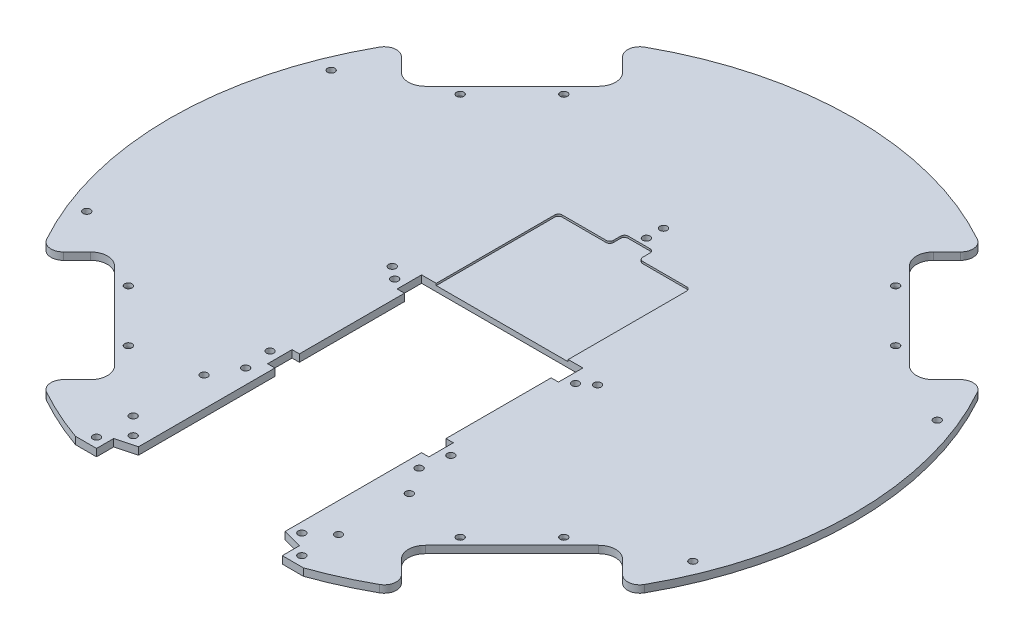
SolidWorks part; units mm, degrees
material "1060 Alloy"
ref_plane "Front Plane" through (0, 0, 0) normal (0, 0, 1) x (1, 0, 0)
ref_plane "Top Plane" through (0, 0, 0) normal (0, 1, 0) x (1, 0, 0)
ref_plane "Right Plane" through (0, 0, 0) normal (1, 0, 0) x (0, 0, -1)
sketch "Sketch1" plane through (0, 0, 0) normal (0, 1, 0) x (1, 0, 0)
  circle A0 centre (0, 0) radius 140
  dimension "D1" = 280
extrude "Boss-Extrude1" add sketch "Sketch1" along normal blind 3
sketch "Sketch7" plane through (0, 3, 0) normal (0, 1, 0) x (1, 0, 0)
  line L0 (-99.0303, -63.6043) -> (-63.6043, -99.0303)
  line L1 (-108.8591, -63.6043) -> (-121.6224, -76.3675)
  line L2 (-63.6043, -108.8591) -> (-76.3675, -121.6224)
  line L3 (-121.6224, -76.3675) -> (-76.3675, -121.6224)
  line L4 (0, 0) -> (-98.9949, -98.9949) construction
  line L7 (0, 0) -> (0, 130) construction
  circle A0 centre (0, 0) radius 140 construction
  arc A1 (-108.8591, -63.6043) -> (-99.0303, -63.6043) centre (-103.9447, -68.5186) cw
  arc A2 (-63.6043, -99.0303) -> (-63.6043, -108.8591) centre (-68.5186, -103.9447) cw
  dimension "D4" = 6.95
  dimension "D1" = 115
  dimension "D2" = 64
  dimension "D3" = 135
extrude "Cut-Extrude4" cut sketch "Sketch7" against normal up to next
sketch "Sketch9" plane through (0, 3, 0) normal (0, 1, 0) x (1, 0, 0)
  line L1 (-63.6043, -99.0303) -> (-99.0303, -63.6043) construction
  line L4 (-108.8591, -63.6043) -> (-119.0017, -73.7469) construction
  circle A0 centre (-89.0955, -67.8823) radius 1.5
  circle A1 centre (-67.8823, -89.0955) radius 1.5
  dimension "D4" = 3
  dimension "D1" = 4
  dimension "D2" = 30
  dimension "D3" = 17
  dimension "D5" = 4
extrude "Cut-Extrude6" cut sketch "Sketch9" against normal up to next
fillet "Fillet1" radius 5 2 edges at (-73.7469, 1.5, 119.0017) (-119.0017, 1.5, 73.7469)
pattern_circular "CirPattern1" count 4 over 360 about axis through (0, 3, 0) along (0, 1, 0) of "Cut-Extrude4", "Fillet1", "Cut-Extrude6"
sketch "Sketch2" plane through (0, 3, 0) normal (0, 1, 0) x (1, 0, 0)
  line L0 (-46.6476, -132) -> (-38, -132)
  line L1 (-30, -122.8564) -> (-30, -67)
  line L2 (-33, -4) -> (33, -4)
  line L3 (30, -67) -> (30, -122.8564)
  line L4 (38, -132) -> (46.6476, -132)
  line L5 (46.6476, -132) -> (46.6476, -140)
  line L6 (46.6476, -140) -> (-46.6476, -140)
  line L7 (-46.6476, -140) -> (-46.6476, -132)
  line L8 (-33, -57) -> (-33, -67)
  line L9 (-33, -67) -> (-30, -67)
  line L10 (33, -57) -> (33, -67)
  line L11 (33, -67) -> (30, -67)
  line L12 (-33, -57) -> (-30, -57)
  line L13 (-30, -57) -> (-30, -14)
  line L14 (-30, -14) -> (-33, -14)
  line L15 (-33, -14) -> (-33, -4)
  line L16 (33, -4) -> (33, -14)
  line L17 (33, -14) -> (30, -14)
  line L18 (30, -14) -> (30, -57)
  line L19 (30, -57) -> (33, -57)
  line L20 (-38, -132) -> (-38, -125)
  line L21 (-38, -125) -> (-30, -122.8564)
  line L22 (38, -132) -> (38, -125)
  line L23 (38, -125) -> (30, -122.8564)
  circle A0 centre (0, 0) radius 140 construction
  dimension "D8" = 3
  dimension "D5" = 63
  dimension "D6" = 66
  dimension "D1" = 8
  dimension "D2" = 65
  dimension "D3" = 60
  dimension "D4" = 16.6476
  dimension "D7" = 10
  dimension "D9" = 76
  dimension "D10" = 7
  dimension "D11" = 105
extrude "Cut-Extrude1" cut sketch "Sketch2" against normal up to next
fillet "Fillet3" radius 1.5 8 edges at (67.8823, 0, 90.5955) (89.0955, 0, 69.3823) (89.0955, 0, -66.3823) (67.8823, 0, -87.5955) (-67.8823, 0, -87.5955) (-89.0955, 0, -66.3823) (-67.8823, 0, 90.5955) (-89.0955, 0, 69.3823)
sketch "Sketch10" plane through (0, 3, 0) normal (0, 1, 0) x (1, 0, 0)
  line L0 (-33, -57) -> (-33, -67) construction
  line L1 (33, -67) -> (33, -57) construction
  line L2 (-33, -67) -> (-30, -67) construction
  line L4 (-30, -14) -> (-33, -14) construction
  line L5 (33, -4) -> (-33, -4) construction
  circle A0 centre (-37, -62) radius 1.5
  circle A1 centre (37, -62) radius 1.5
  circle A2 centre (-37, -11) radius 1.5
  circle A3 centre (37, -11) radius 1.5
  circle A4 centre (-42, -7) radius 1.5
  circle A5 centre (42, -7) radius 1.5
  point P17 (-31.5, -14)
  dimension "D3" = 3
  dimension "D1" = 4
  dimension "D2" = 4
  dimension "D4" = 5
  dimension "D5" = 3
  dimension "D6" = 3
  dimension "D7" = 5
  dimension "D8" = 5
extrude "Cut-Extrude7" cut sketch "Sketch10" against normal up to next
sketch "Sketch13" plane through (0, 3, 0) normal (0, 1, 0) x (1, 0, 0)
  line L0 (-38, -132) -> (-46.6476, -132) construction
  line L1 (-38, -132) -> (-46.6476, -132) construction
  circle A0 centre (-42, -84) radius 1.5
  circle A1 centre (-42, -113) radius 1.5
  circle A2 centre (42, -113) radius 1.5
  circle A3 centre (42, -84) radius 1.5
  dimension "D1" = 3
  dimension "D2" = 19
  dimension "D3" = 48
  dimension "D4" = 42
  dimension "D5" = 42
extrude "Cut-Extrude9" cut sketch "Sketch13" against normal up to next
sketch "Sketch16" plane through (0, 3, 0) normal (0, 1, 0) x (1, 0, 0)
  circle A0 centre (0, 62) radius 1.5
  circle A4 centre (0, 55) radius 1.5
  dimension "D2" = 3
  dimension "D5" = 3
  dimension "D1" = 62
  dimension "D7" = 55
extrude "Cut-Extrude12" cut sketch "Sketch16" against normal up to next
sketch "Sketch17" plane through (0, 3, 0) normal (0, 1, 0) x (1, 0, 0)
  circle A0 centre (-124, 50) radius 1.5
  circle A1 centre (-124, -50) radius 1.5
  circle A2 centre (124, 50) radius 1.5
  circle A3 centre (124, -50) radius 1.5
  dimension "D1" = 3
  dimension "D2" = 50
  dimension "D3" = 50
  dimension "D4" = 124
  dimension "D5" = 124
extrude "Cut-Extrude13" cut sketch "Sketch17" against normal up to next
sketch "Sketch18" plane through (0, 3, 0) normal (0, 1, 0) x (1, 0, 0)
  line L1 (-27, -4) -> (27, -4)
  line L2 (-27, -4) -> (-27, 46)
  line L3 (-27, 46) -> (27, 46)
  line L4 (27, -4) -> (27, 46)
  line L5 (33, -4) -> (-33, -4) construction
  dimension "D1" = 50
  dimension "D2" = 54
  dimension "D3" = 27
extrude "Cut-Extrude14" cut sketch "Sketch18" against normal blind 0.8
sketch "Sketch19" plane through (0, 3, 0) normal (0, 1, 0) x (1, 0, 0)
  line L0 (-38, -125) -> (-38, -132) construction
  line L1 (-38, -132) -> (-46.6476, -132) construction
  line L2 (38, -132) -> (38, -125) construction
  circle A0 centre (-42, -128) radius 1.5
  circle A1 centre (42, -128) radius 1.5
  dimension "D4" = 3
  dimension "D1" = 4
  dimension "D2" = 4
  dimension "D3" = 4
extrude "Cut-Extrude15" cut sketch "Sketch19" against normal up to next
sketch "Sketch20" plane through (0, 3, 0) normal (0, 1, 0) x (1, 0, 0)
  line L0 (27, 46) -> (-27, 46) construction
  line L1 (-6, 46) -> (6, 46)
  line L2 (-6, 46) -> (-6, 52)
  line L3 (-6, 52) -> (6, 52)
  line L4 (6, 46) -> (6, 52)
  circle A0 centre (0, 55) radius 1.5 construction
  dimension "D1" = 12
  dimension "D2" = 6
  dimension "D3" = 3
extrude "Cut-Extrude16" cut sketch "Sketch20" against normal up to surface (0.8 mm away) up to face at (0, 2.2, -21)
fillet "Fillet4" radius 1.5 6 edges at (6, 2.6, -46) (27, 2.6, -46) (-27, 2.6, -46) (-6, 2.6, -46) (6, 2.6, -52) (-6, 2.6, -52)
sketch "Sketch21" plane through (0, 3, 0) normal (0, 1, 0) x (1, 0, 0)
  circle A0 centre (-35, -120) radius 1.5
  circle A1 centre (-36, -73) radius 1.5
  circle A2 centre (34, -120) radius 1.5
  circle A3 centre (35, -73) radius 1.5
  circle A4 centre (-42, -128) radius 1.5 construction
  circle A5 centre (42, -128) radius 1.5 construction
  dimension "D1" = 7
  dimension "D3" = 3
  dimension "D2" = 8
  dimension "D4" = 47
  dimension "D5" = 1
  dimension "D6" = 1
  dimension "D7" = 8
extrude "Cut-Extrude17" cut sketch "Sketch21" against normal up to next
